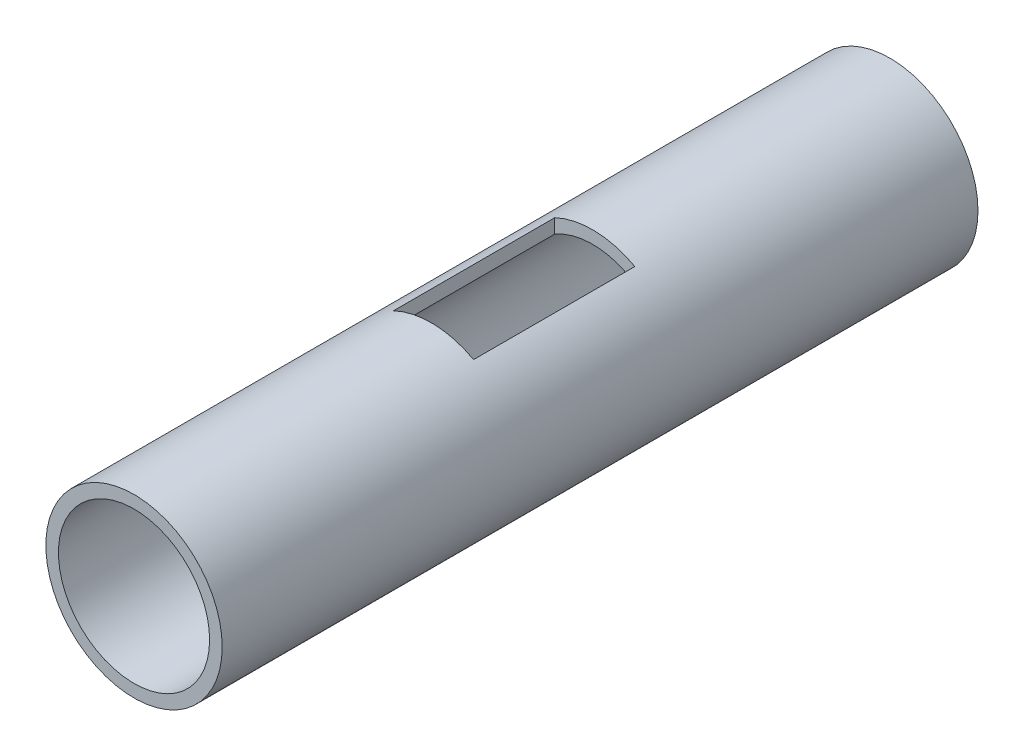
SolidWorks part; units mm, degrees
ref_plane "Plano frontal" through (0, 0, 0) normal (0, 0, 1) x (1, 0, 0)
ref_plane "Plano superior" through (0, 0, 0) normal (0, 1, 0) x (1, 0, 0)
ref_plane "Plano direito" through (0, 0, 0) normal (1, 0, 0) x (0, 0, -1)
sketch "Esboço1" plane through (0, 0, 0) normal (0, 0, 1) x (1, 0, 0)
  circle A0 centre (-19.4422, 6.3987) radius 7
extrude "Ressalto-extrusão1" add sketch "Esboço1" along normal blind 60
sketch "Esboço2" plane through (0, 0, 60) normal (0, 0, 1) x (1, 0, 0)
  circle A0 centre (-19.4422, 6.3987) radius 6
extrude "Corte-extrusão1" cut sketch "Esboço2" against normal blind 71
sketch "Esboço3" plane through (0, 0, 0) normal (0, 1, 0) x (1, 0, 0)
  line L0 (-26.4422, -60) -> (-12.4422, -60) construction
  line L1 (-22.4445, -23.6) -> (-16.0868, -23.6)
  line L2 (-22.4445, -23.6) -> (-22.4445, -36.3968)
  line L3 (-22.4445, -36.3968) -> (-16.0868, -36.3968)
  line L4 (-16.0868, -23.6) -> (-16.0868, -36.3968)
  line L5 (-12.4422, 0) -> (-26.4422, 0) construction
  dimension "D1" = 23.6032
  dimension "D2" = 23.6
extrude "Corte-extrusão2" cut sketch "Esboço3" along normal blind 21 and the other way blind 21
